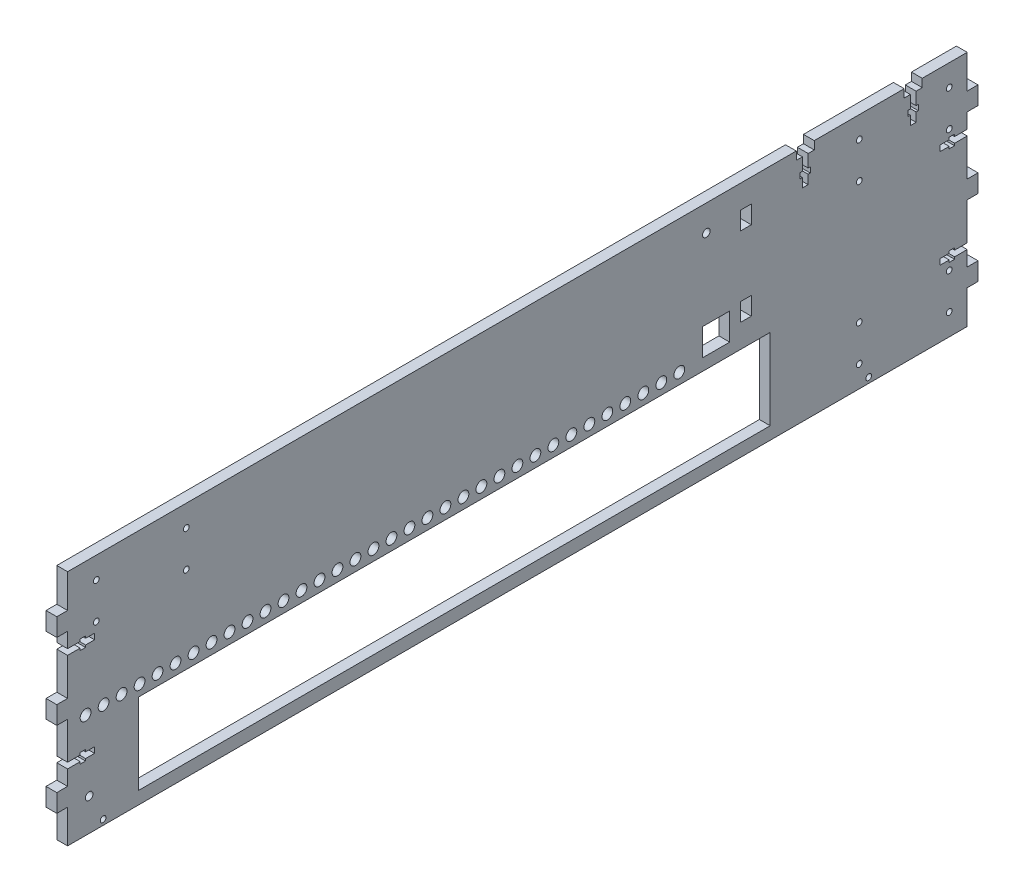
SolidWorks part; units mm, degrees
ref_plane "Front Plane" through (0, 0, 0) normal (0, 0, 1) x (1, 0, 0)
ref_plane "Top Plane" through (0, 0, 0) normal (0, 1, 0) x (1, 0, 0)
ref_plane "Right Plane" through (0, 0, 0) normal (1, 0, 0) x (0, 0, -1)
sketch "Sketch1" plane through (0, 0, 0) normal (1, 0, 0) x (0, 0, -1)
  line L1 (-250, -66) -> (250, -66)
  line L2 (-250, -66) -> (-250, 66)
  line L3 (-250, 66) -> (250, 66)
  line L4 (250, -66) -> (250, 66)
  line L5 (-250, -66) -> (250, 66) construction
  line L6 (-250, 66) -> (250, -66) construction
  point P0 (0, 0)
  dimension "D1" = 132
  dimension "D2" = 500
extrude "Boss-Extrude1" add sketch "Sketch1" along normal blind 6
sketch "Sketch4" plane through (0, 0, 250) normal (0, 0, 1) x (1, 0, 0)
  line L0 (0, 66) -> (0, -66) construction
  line L1 (0, 47.3321) -> (6, 47.3321)
  line L2 (0, 47.3321) -> (0, 37.3321)
  line L3 (0, 37.3321) -> (6, 37.3321)
  line L4 (6, 47.3321) -> (6, 37.3321)
  line L5 (6, 66) -> (6, -66) construction
  line L6 (0, 37.3321) -> (6, 37.3321) construction
  line L7 (0, -66) -> (0, 66) construction
  line L8 (6, 47.3321) -> (0, 47.3321) construction
  line L9 (0, -5) -> (6, -5) construction
  line L10 (0, -5) -> (6, -5)
  line L11 (0, -5) -> (0, 5)
  line L12 (0, 5) -> (6, 5)
  line L13 (6, -5) -> (6, 5)
  line L14 (6, -66) -> (6, 66) construction
  line L15 (6, 5) -> (0, 5) construction
  line L16 (6, -37.3321) -> (0, -37.3321) construction
  line L17 (0, -47.3321) -> (6, -47.3321)
  line L18 (0, -47.3321) -> (0, -37.3321)
  line L19 (0, -37.3321) -> (6, -37.3321)
  line L20 (6, -47.3321) -> (6, -37.3321)
  line L21 (0, -47.3321) -> (6, -47.3321) construction
extrude "Boss-Extrude2" add sketch "Sketch4" along normal blind 6
sketch "Sketch5" plane through (0, 0, 0) normal (-1, 0, 0) x (0, 0, 1)
  line L1 (250, 28.9321) -> (250, 25.7321) construction
  line L3 (250, 28.9321) -> (250, 25.7321) construction
  line L4 (250, -25.7321) -> (250, -28.9321) construction
  line L5 (250, -25.7321) -> (250, -28.9321) construction
  line L6 (250, 27.3321) -> (235, 27.3321) construction
  line L7 (250, -27.3321) -> (235, -27.3321) construction
  line L8 (250, -25.7321) -> (243, -25.7321)
  line L9 (250, 28.9321) -> (243, 28.9321)
  line L10 (250, -28.9321) -> (243, -28.9321)
  line L11 (250, 25.7321) -> (243, 25.7321)
  line L12 (250, -25.7321) -> (250, -28.9321)
  line L13 (235, -25.7321) -> (235, -28.9321)
  line L14 (250, 28.9321) -> (250, 25.7321)
  line L15 (235, 28.9321) -> (235, 25.7321)
  line L16 (240, 25.7321) -> (235, 25.7321)
  line L17 (243, 24.5321) -> (240, 24.5321)
  line L18 (243, 24.5321) -> (243, 25.7321)
  line L19 (243, 30.1321) -> (240, 30.1321)
  line L20 (240, 24.5321) -> (240, 25.7321)
  line L21 (243, 24.5321) -> (240, 30.1321) construction
  line L22 (243, 30.1321) -> (240, 24.5321) construction
  line L23 (243, -30.1321) -> (240, -30.1321)
  line L24 (243, -30.1321) -> (243, -28.9321)
  line L25 (243, -24.5321) -> (240, -24.5321)
  line L26 (240, -30.1321) -> (240, -28.9321)
  line L27 (243, -30.1321) -> (240, -24.5321) construction
  line L28 (243, -24.5321) -> (240, -30.1321) construction
  line L29 (250, 25.7321) -> (235, 25.7321) construction
  line L30 (243, 28.9321) -> (243, 30.1321)
  line L31 (240, 28.9321) -> (235, 28.9321)
  line L32 (250, 28.9321) -> (235, 28.9321) construction
  line L33 (240, 28.9321) -> (240, 30.1321)
  line L34 (240, -25.7321) -> (235, -25.7321)
  line L35 (250, -25.7321) -> (235, -25.7321) construction
  line L36 (240, -25.7321) -> (240, -24.5321)
  line L37 (240, -28.9321) -> (235, -28.9321)
  line L38 (250, -28.9321) -> (235, -28.9321) construction
  line L39 (243, -25.7321) -> (243, -24.5321)
  point P20 (241.5, 27.3321)
  point P25 (241.5, -27.3321)
  line M35 (250, -37.3321) -> (250, -5)
  line M39 (250, 5) -> (250, 37.3321)
  dimension "D3" = 1.6
  dimension "D4" = 7
  dimension "D5" = 3
  dimension "D6" = 5.6
  dimension "D1" = 15
  dimension "D7" = 7
  dimension "D8" = 3
  dimension "D9" = 5.6
  dimension "D2" = 1.6
extrude "Cut-Extrude3" cut sketch "Sketch5" against normal up to next contours L12 | L8 L39 L25 L36 L34 L13 L37 L26 L23 L24 L10 M35 | L33 L31 L15 L16 L20 L17 L18 L11 L9 L30 L19 M39 region at (0, -27.3321, 242.3696) region at (0, 27.3321, 242.3696)
sketch "Sketch6" plane through (0, 0, -250) normal (0, 0, -1) x (-1, 0, 0)
  line L0 (0, 47.3321) -> (0, 37.3321) construction
  line L1 (0, 37.3321) -> (-6, 37.3321) construction
  line L2 (-6, 37.3321) -> (-6, 47.3321) construction
  line L3 (-6, 47.3321) -> (0, 47.3321) construction
  line L4 (0, 5) -> (0, -5) construction
  line L5 (0, -5) -> (-6, -5) construction
  line L6 (-6, -5) -> (-6, 5) construction
  line L7 (-6, 5) -> (0, 5) construction
  line L8 (0, -37.3321) -> (0, -47.3321) construction
  line L9 (0, -47.3321) -> (-6, -47.3321) construction
  line L10 (-6, -47.3321) -> (-6, -37.3321) construction
  line L11 (-6, -37.3321) -> (0, -37.3321) construction
  line L12 (0, 47.3321) -> (0, 37.3321)
  line L13 (0, 37.3321) -> (-6, 37.3321)
  line L14 (-6, 37.3321) -> (-6, 47.3321)
  line L15 (-6, 47.3321) -> (0, 47.3321)
  line L16 (0, 5) -> (0, -5)
  line L17 (0, -5) -> (-6, -5)
  line L18 (-6, -5) -> (-6, 5)
  line L19 (-6, 5) -> (0, 5)
  line L20 (0, -37.3321) -> (0, -47.3321)
  line L21 (0, -47.3321) -> (-6, -47.3321)
  line L22 (-6, -47.3321) -> (-6, -37.3321)
  line L23 (-6, -37.3321) -> (0, -37.3321)
extrude "Boss-Extrude3" add sketch "Sketch6" along normal blind 6
sketch "Sketch7" plane through (0, 0, 0) normal (-1, 0, 0) x (0, 0, 1)
  line L0 (243, 25.7321) -> (250, 25.7321) construction
  line L2 (243, 25.7321) -> (243, 24.5321) construction
  line L3 (240, 24.5321) -> (243, 24.5321) construction
  line L4 (240, 25.7321) -> (240, 24.5321) construction
  line L5 (235, 25.7321) -> (240, 25.7321) construction
  line L6 (235, 25.7321) -> (235, 28.9321) construction
  line L7 (235, 28.9321) -> (240, 28.9321) construction
  line L8 (240, 30.1321) -> (240, 28.9321) construction
  line L9 (240, 30.1321) -> (243, 30.1321) construction
  line L10 (243, 30.1321) -> (243, 28.9321) construction
  line L11 (243, 28.9321) -> (250, 28.9321) construction
  line L12 (243, 25.7321) -> (250, 25.7321) construction
  line L13 (243, 25.7321) -> (243, 24.5321) construction
  line L14 (240, 24.5321) -> (243, 24.5321) construction
  line L15 (240, 25.7321) -> (240, 24.5321) construction
  line L16 (235, 25.7321) -> (240, 25.7321) construction
  line L17 (235, 25.7321) -> (235, 28.9321) construction
  line L18 (235, 28.9321) -> (240, 28.9321) construction
  line L19 (240, 30.1321) -> (240, 28.9321) construction
  line L20 (240, 30.1321) -> (243, 30.1321) construction
  line L21 (243, 30.1321) -> (243, 28.9321) construction
  line L22 (243, 28.9321) -> (250, 28.9321) construction
  line L23 (235, -28.9321) -> (240, -28.9321) construction
  line L24 (240, -28.9321) -> (240, -30.1321) construction
  line L25 (240, -30.1321) -> (243, -30.1321) construction
  line L26 (243, -28.9321) -> (243, -30.1321) construction
  line L27 (243, -28.9321) -> (250, -28.9321) construction
  line L28 (243, -25.7321) -> (250, -25.7321) construction
  line L29 (243, -24.5321) -> (243, -25.7321) construction
  line L30 (240, -24.5321) -> (243, -24.5321) construction
  line L31 (240, -24.5321) -> (240, -25.7321) construction
  line L32 (235, -25.7321) -> (240, -25.7321) construction
  line L33 (235, -28.9321) -> (235, -25.7321) construction
  line L34 (235, -28.9321) -> (240, -28.9321) construction
  line L35 (240, -28.9321) -> (240, -30.1321) construction
  line L36 (240, -30.1321) -> (243, -30.1321) construction
  line L37 (243, -28.9321) -> (243, -30.1321) construction
  line L38 (243, -28.9321) -> (250, -28.9321) construction
  line L39 (243, -25.7321) -> (250, -25.7321) construction
  line L40 (243, -24.5321) -> (243, -25.7321) construction
  line L41 (240, -24.5321) -> (243, -24.5321) construction
  line L42 (240, -24.5321) -> (240, -25.7321) construction
  line L43 (235, -25.7321) -> (240, -25.7321) construction
  line L44 (235, -28.9321) -> (235, -25.7321) construction
  line L45 (0, 0) -> (0, 57.5645) construction
  line L46 (-235, -28.9321) -> (-235, -25.7321)
  line L47 (-235, -25.7321) -> (-240, -25.7321)
  line L48 (-240, -24.5321) -> (-240, -25.7321)
  line L49 (-240, -24.5321) -> (-243, -24.5321)
  line L50 (-243, -24.5321) -> (-243, -25.7321)
  line L51 (-243, -25.7321) -> (-250, -25.7321)
  line L52 (-243, -28.9321) -> (-250, -28.9321)
  line L53 (-243, -28.9321) -> (-243, -30.1321)
  line L54 (-240, -30.1321) -> (-243, -30.1321)
  line L55 (-240, -28.9321) -> (-240, -30.1321)
  line L56 (-235, -28.9321) -> (-240, -28.9321)
  line L57 (-243, 28.9321) -> (-250, 28.9321)
  line L58 (-243, 30.1321) -> (-243, 28.9321)
  line L59 (-240, 30.1321) -> (-243, 30.1321)
  line L60 (-240, 30.1321) -> (-240, 28.9321)
  line L61 (-235, 28.9321) -> (-240, 28.9321)
  line L62 (-235, 25.7321) -> (-235, 28.9321)
  line L63 (-235, 25.7321) -> (-240, 25.7321)
  line L64 (-240, 25.7321) -> (-240, 24.5321)
  line L65 (-240, 24.5321) -> (-243, 24.5321)
  line L66 (-243, 25.7321) -> (-243, 24.5321)
  line L67 (-243, 25.7321) -> (-250, 25.7321)
  line L68 (-250, 28.9321) -> (-250, 25.7321)
  line L69 (-250, -25.7321) -> (-250, -28.9321)
extrude "Cut-Extrude4" cut sketch "Sketch7" against normal up to next
sketch "Sketch8" plane through (0, 0, 0) normal (-1, 0, 0) x (0, 0, 1)
  line L0 (210, -14.55) -> (-140, -14.55) construction
  line L1 (210, -14.55) -> (-140, -14.55) construction
  line L2 (210, -14.55) -> (210, -59) construction
  line L3 (210, -14.55) -> (210, -59) construction
  line L186 (-140, -14.55) -> (-140, -59) construction
  line L187 (-140, -59) -> (210, -59) construction
  line L188 (210.5, -14.05) -> (210.5, -59)
  line L189 (210.5, -14.05) -> (-140.5, -14.05)
  line L190 (-140.5, -14.05) -> (-140.5, -59)
  line L191 (-140.5, -59) -> (210.5, -59)
  dimension "D1" = 0.5
extrude "Cut-Extrude5" cut sketch "Sketch8" against normal up to next
sketch "Sketch11" plane through (6, 0, 0) normal (1, 0, 0) x (0, 0, -1)
  line L0 (130, 43) -> (130, 53) construction
  line L1 (130, 53) -> (124, 53) construction
  line L2 (124, 53) -> (124, 43) construction
  line L3 (124, 43) -> (130, 43) construction
  line L4 (130, -1) -> (130, 9) construction
  line L5 (130, 9) -> (124, 9) construction
  line L6 (124, 9) -> (124, -1) construction
  line L7 (124, -1) -> (130, -1) construction
  line L8 (130, 43) -> (130, 53)
  line L9 (130, 53) -> (124, 53)
  line L10 (124, 53) -> (124, 43)
  line L11 (124, 43) -> (130, 43)
  line L12 (130, -1) -> (130, 9)
  line L13 (130, 9) -> (124, 9)
  line L14 (124, 9) -> (124, -1)
  line L15 (124, -1) -> (130, -1)
extrude "Cut-Extrude8" cut sketch "Sketch11" against normal up to next
sketch "Sketch12" plane through (0, 0, 0) normal (-1, 0, 0) x (0, 0, 1)
  line L0 (-124, 53) -> (-124, 43) construction
  line L1 (-250, 66) -> (250, 66) construction
  circle A0 centre (-105, 51.5) radius 2.1
  dimension "D1" = 19
  dimension "D3" = 4.2
  dimension "D2" = 14.5
extrude "Cut-Extrude9" cut sketch "Sketch12" against normal up to next
sketch "Sketch13" plane through (0, 66, 0) normal (0, 1, 0) x (1, 0, 0)
  line L0 (6, 250) -> (6, -250) construction
  line L1 (0, 215) -> (6, 215)
  line L2 (0, 215) -> (0, 225)
  line L3 (0, 225) -> (6, 225)
  line L4 (6, 215) -> (6, 225)
  line L5 (0, 215) -> (6, 225) construction
  line L6 (0, 225) -> (6, 215) construction
  line L7 (6, 225) -> (0, 225) construction
  line L8 (6, 165) -> (0, 165) construction
  line L9 (0, 155) -> (6, 155)
  line L10 (0, 155) -> (0, 165)
  line L11 (0, 165) -> (6, 165)
  line L12 (6, 155) -> (6, 165)
  line L13 (0, 155) -> (6, 165) construction
  line L14 (0, 165) -> (6, 155) construction
  point P0 (3, 220)
  point P10 (3, 160)
extrude "Cut-Extrude10" cut sketch "Sketch13" against normal blind 4.5
sketch "Sketch14" plane through (0, 0, 0) normal (-1, 0, 0) x (0, 0, 1)
  circle A0 centre (240, -8) radius 3 construction
  circle A1 centre (240, -8) radius 3
  circle A2 centre (230, -8) radius 3
  circle A3 centre (220, -8) radius 3
  circle A4 centre (210, -8) radius 3
  circle A5 centre (200, -8) radius 3
  circle A6 centre (190, -8) radius 3
  circle A7 centre (180, -8) radius 3
  circle A8 centre (170, -8) radius 3
  circle A9 centre (160, -8) radius 3
  circle A10 centre (150, -8) radius 3
  circle A11 centre (140, -8) radius 3
  circle A12 centre (130, -8) radius 3
  circle A13 centre (120, -8) radius 3
  circle A14 centre (110, -8) radius 3
  circle A15 centre (100, -8) radius 3
  circle A16 centre (90, -8) radius 3
  circle A17 centre (80, -8) radius 3
  circle A18 centre (70, -8) radius 3
  circle A19 centre (60, -8) radius 3
  circle A20 centre (50, -8) radius 3
  circle A21 centre (40, -8) radius 3
  circle A22 centre (30, -8) radius 3
  circle A23 centre (20, -8) radius 3
  circle A24 centre (10, -8) radius 3
  circle A25 centre (0, -8) radius 3
  circle A26 centre (-10, -8) radius 3
  circle A27 centre (-20, -8) radius 3
  circle A28 centre (-30, -8) radius 3
  circle A29 centre (-40, -8) radius 3
  circle A30 centre (-50, -8) radius 3
  circle A31 centre (-60, -8) radius 3
  circle A32 centre (-70, -8) radius 3
  circle A33 centre (-80, -8) radius 3
  circle A34 centre (-90, -8) radius 3
  dimension "D1" = 34
extrude "Cut-Extrude11" cut sketch "Sketch14" against normal up to next (6 mm away)
sketch "Sketch15" plane through (6, 0, 0) normal (1, 0, 0) x (0, 0, -1)
  line L0 (160, 61.5) -> (160, 46.5) construction
  line L1 (155, 61.5) -> (165, 61.5) construction
  line L2 (220, 61.5) -> (220, 46.5) construction
  line L3 (215, 61.5) -> (225, 61.5) construction
  line L4 (160, 46.5) -> (220, 46.5) construction
  line L5 (190, 46.5) -> (190, 66) construction
  line L6 (215, 66) -> (165, 66) construction
  line L7 (158.4, 61.5) -> (158.4, 54.5)
  line L8 (161.6, 61.5) -> (161.6, 54.5)
  line L9 (158.4, 61.5) -> (161.6, 61.5)
  line L10 (158.4, 46.5) -> (161.6, 46.5)
  line L11 (161.6, 51.5) -> (162.8, 51.5)
  line L12 (157.2, 54.5) -> (158.4, 54.5)
  line L13 (157.2, 54.5) -> (157.2, 51.5)
  line L14 (157.2, 51.5) -> (158.4, 51.5)
  line L15 (162.8, 54.5) -> (162.8, 51.5)
  line L16 (157.2, 54.5) -> (162.8, 51.5) construction
  line L17 (157.2, 51.5) -> (162.8, 54.5) construction
  line L18 (161.6, 54.5) -> (162.8, 54.5)
  line L19 (158.4, 51.5) -> (158.4, 46.5)
  line L20 (158.4, 61.5) -> (158.4, 46.5) construction
  line L21 (161.6, 51.5) -> (161.6, 46.5)
  line L22 (161.6, 61.5) -> (161.6, 46.5) construction
  line L23 (222.8, 51.5) -> (217.2, 54.5) construction
  line L24 (222.8, 54.5) -> (217.2, 51.5) construction
  line L25 (220, 61.5) -> (220, 46.5) construction
  line L26 (218.4, 51.5) -> (218.4, 46.5)
  line L27 (221.6, 51.5) -> (221.6, 46.5)
  line L28 (218.4, 54.5) -> (217.2, 54.5)
  line L29 (217.2, 54.5) -> (217.2, 51.5)
  line L30 (222.8, 51.5) -> (221.6, 51.5)
  line L31 (222.8, 54.5) -> (222.8, 51.5)
  line L32 (222.8, 54.5) -> (221.6, 54.5)
  line L33 (218.4, 51.5) -> (217.2, 51.5)
  line L34 (221.6, 46.5) -> (218.4, 46.5)
  line L35 (221.6, 61.5) -> (218.4, 61.5)
  line L36 (218.4, 61.5) -> (218.4, 54.5)
  line L37 (221.6, 61.5) -> (221.6, 54.5)
  point P16 (160, 53)
  point P37 (220, 53)
  dimension "D3" = 15
  dimension "D4" = 7
  dimension "D5" = 3
  dimension "D6" = 5.6
  dimension "D1" = 1.6
  dimension "D2" = 1.6
extrude "Cut-Extrude12" cut sketch "Sketch15" against normal up to next
sketch "Sketch17" plane through (6, 0, 0) normal (1, 0, 0) x (0, 0, -1)
  circle A0 centre (-238, -48) radius 2.1 construction
  circle A1 centre (-238, -48) radius 2.1
extrude "Cut-Extrude14" cut sketch "Sketch17" against normal through all
sketch "Sketch18" plane through (6, 0, 0) normal (1, 0, 0) x (0, 0, -1)
  line L0 (-210.5, -59) -> (-250, -59) construction
  line L1 (-250, -47.3321) -> (-250, -66) construction
  line L2 (-230.25, -59) -> (-230.25, -66) construction
  line L3 (-250, -66) -> (250, -66) construction
  line L4 (140.5, -59) -> (250, -59) construction
  line L5 (250, -66) -> (250, -47.3321) construction
  line L6 (195.25, -59) -> (195.25, -66) construction
  circle A0 centre (-230.25, -63) radius 1.6
  circle A1 centre (195.25, -63) radius 1.6
  dimension "D1" = 3.2
  dimension "D2" = 3
extrude "Cut-Extrude15" cut sketch "Sketch18" against normal through all
sketch "Sketch19" plane through (6, 0, 0) normal (1, 0, 0) x (0, 0, -1)
  circle A1 centre (240, -34) radius 1.6
  circle A2 centre (240, -34) radius 1.6
  circle A3 centre (240, 54) radius 1.6
  circle A5 centre (240, 54) radius 1.6
  circle A7 centre (240, -54) radius 1.6
  circle A8 centre (240, -54) radius 1.6
  circle A11 centre (190, -54) radius 1.6
  circle A12 centre (190, -54) radius 1.6
  circle A15 centre (190, -34) radius 1.6
  circle A16 centre (190, -34) radius 1.6
  circle A24 centre (190, 34) radius 1.6
  circle A25 centre (190, 34) radius 1.6
  circle A30 centre (190, 54) radius 1.6
  circle A31 centre (190, 54) radius 1.6
  circle A32 centre (240, 34) radius 1.6
  circle A33 centre (240, 34) radius 1.6
  circle A56 centre (-184, 34) radius 1.6 construction
  circle A57 centre (-234, 34) radius 1.6 construction
  circle A58 centre (-184, 54) radius 1.6 construction
  circle A59 centre (-234, 54) radius 1.6 construction
  circle A60 centre (-184, 34) radius 1.6
  circle A61 centre (-234, 34) radius 1.6
  circle A62 centre (-184, 54) radius 1.6
  circle A63 centre (-234, 54) radius 1.6
  dimension "D1" = 0
  dimension "D2" = 0
  dimension "D5" = 0
  dimension "D7" = 0
  dimension "D9" = 0
  dimension "D12" = 0
  dimension "D15" = 0
  dimension "D16" = 0
extrude "Cut-Extrude16" cut sketch "Sketch19" against normal through all
sketch "Sketch20" plane through (6, 0, 0) normal (1, 0, 0) x (0, 0, -1)
  line L0 (-250, 22) -> (251, 22) construction
  line L1 (-250, 22) -> (251, 22) construction
  line L2 (-250, -22) -> (251, -22) construction
  line L3 (-250, -22) -> (251, -22) construction
  line L4 (118, 22) -> (118, -22) construction
  line L5 (124, 9) -> (124, -1) construction
  line L6 (118, 0) -> (103, 0) construction
  line L7 (118, 7.5) -> (103, 7.5)
  line L8 (118, -7.5) -> (103, -7.5)
  line L9 (118, 7.5) -> (118, -7.5)
  line L10 (103, 7.5) -> (103, -7.5)
  point P8 (124, 4)
  dimension "D1" = 6
  dimension "D2" = 15
  dimension "D3" = 7.5
  dimension "D4" = 7.5
extrude "Cut-Extrude17" cut sketch "Sketch20" against normal through all
